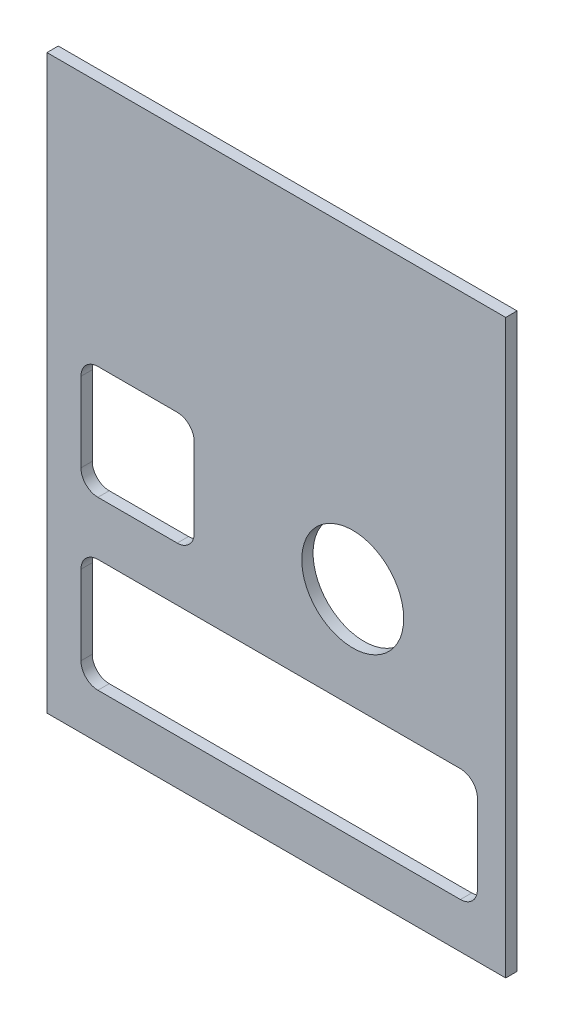
SolidWorks part; units mm, degrees
ref_plane "Front Plane" through (0, 0, 0) normal (0, 0, 1) x (1, 0, 0)
ref_plane "Top Plane" through (0, 0, 0) normal (0, 1, 0) x (1, 0, 0)
ref_plane "Right Plane" through (0, 0, 0) normal (1, 0, 0) x (0, 0, -1)
sketch "Sketch1" plane through (0, 0, 0) normal (0, 0, 1) x (1, 0, 0)
  line L1 (-48.8946, 55.0473) -> (32.1054, 55.0473)
  line L2 (-48.8946, 55.0473) -> (-48.8946, -45.9527)
  line L3 (-48.8946, -45.9527) -> (32.1054, -45.9527)
  line L4 (32.1054, 55.0473) -> (32.1054, -45.9527)
extrude "Boss-Extrude1" add sketch "Sketch1" along normal blind 2
sketch "Sketch2" plane through (0, 0, 2) normal (0, 0, 1) x (1, 0, 0)
  line L3 (-39.8946, -17.9527) -> (24.1054, -17.9527)
  line L4 (-42.8946, -20.9527) -> (-42.8946, -34.9527)
  line L5 (-39.8946, -37.9527) -> (24.1054, -37.9527)
  line L6 (27.1054, -20.9527) -> (27.1054, -34.9527)
  line L7 (-48.8946, 55.0473) -> (-48.8946, -45.9527) construction
  line L8 (-48.8946, -45.9527) -> (32.1054, -45.9527) construction
  line L15 (-39.8946, 11.5473) -> (-25.8946, 11.5473)
  line L16 (-42.8946, 8.5473) -> (-42.8946, -5.4527)
  line L17 (-39.8946, -8.4527) -> (-25.8946, -8.4527)
  line L18 (-22.8946, 8.5473) -> (-22.8946, -5.4527)
  line L19 (32.1054, -45.9527) -> (32.1054, 55.0473) construction
  arc A2 (24.1054, -17.9527) -> (27.1054, -20.9527) centre (24.1054, -20.9527) cw
  arc A3 (-42.8946, -34.9527) -> (-39.8946, -37.9527) centre (-39.8946, -34.9527) ccw
  arc A4 (24.1054, -37.9527) -> (27.1054, -34.9527) centre (24.1054, -34.9527) ccw
  arc A5 (-39.8946, -17.9527) -> (-42.8946, -20.9527) centre (-39.8946, -20.9527) ccw
  arc A6 (-42.8946, -5.4527) -> (-39.8946, -8.4527) centre (-39.8946, -5.4527) ccw
  arc A7 (-25.8946, -8.4527) -> (-22.8946, -5.4527) centre (-25.8946, -5.4527) ccw
  arc A8 (-25.8946, 11.5473) -> (-22.8946, 8.5473) centre (-25.8946, 8.5473) cw
  arc A9 (-39.8946, 11.5473) -> (-42.8946, 8.5473) centre (-39.8946, 8.5473) ccw
  circle A10 centre (5.0914, 0) radius 9
  point P11 (27.1054, -17.9527)
  point P14 (-42.8946, -37.9527)
  point P18 (27.1054, -37.9527)
  point P27 (-22.8946, -8.4527)
  point P30 (-22.8946, 11.5473)
  point P33 (-42.8946, 11.5473)
  dimension "D1" = 70
  dimension "D5" = 3
  dimension "D6" = 3
  dimension "D11" = 3
  dimension "D12" = 18
  dimension "D13" = 18.014
  dimension "D14" = 8.9527
  dimension "D2" = 6
  dimension "D3" = 20
  dimension "D4" = 8
  dimension "D7" = 20
  dimension "D8" = 20
  dimension "D9" = 6
  dimension "D10" = 9.5
extrude "Cut-Extrude2" cut sketch "Sketch2" against normal blind 2
